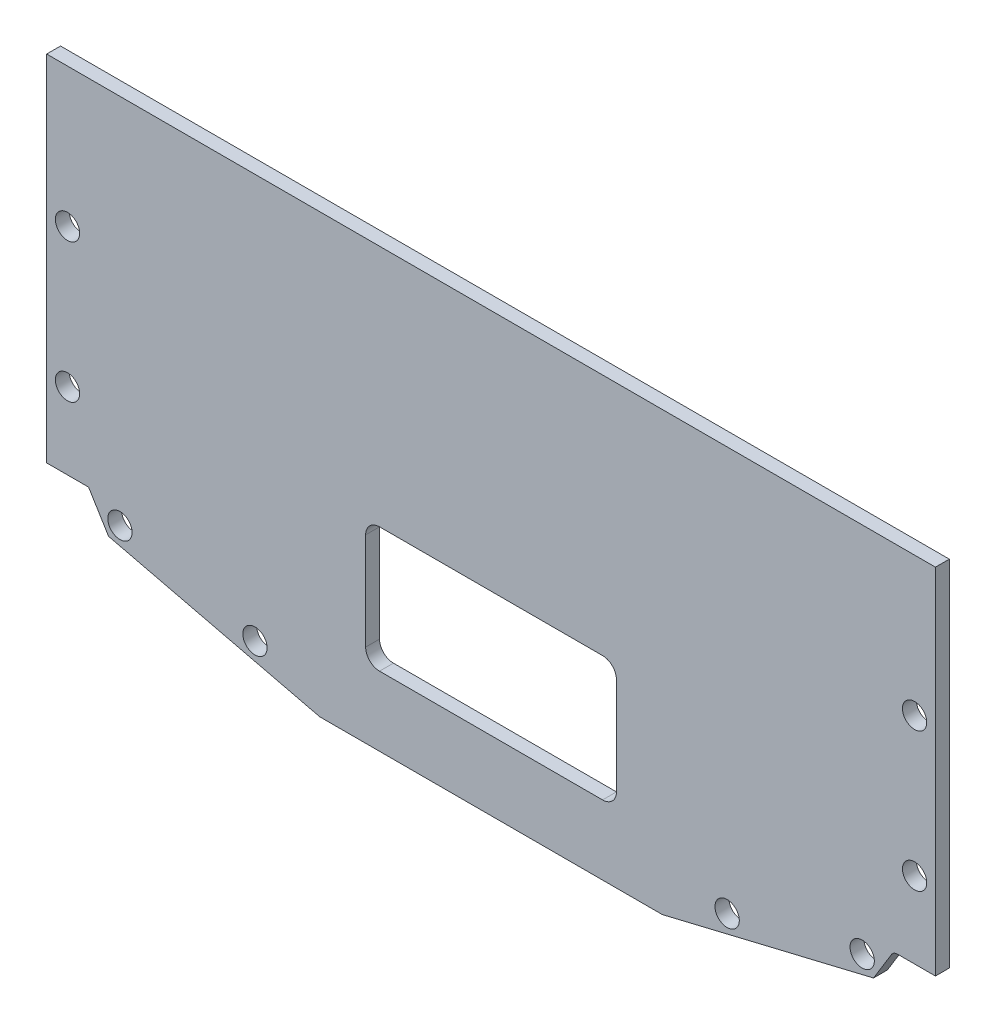
SolidWorks part; units mm, degrees
material "Thornel Mat VMA"
ref_plane "前视基准面" through (0, 0, 0) normal (0, 0, 1) x (1, 0, 0)
ref_plane "上视基准面" through (0, 0, 0) normal (0, 1, 0) x (1, 0, 0)
ref_plane "右视基准面" through (0, 0, 0) normal (1, 0, 0) x (0, 0, -1)
sketch "草图1" plane through (0, 0, 0) normal (0, 0, 1) x (1, 0, 0)
  line L0 (0, 63) -> (-21.7241, 8.6897) construction
  line L1 (0, 0) -> (128, 0)
  line L2 (0, 0) -> (0, 63)
  line L3 (0, 63) -> (128, 63)
  line L4 (128, 0) -> (128, 63)
  line L5 (-21.7241, 8.6897) -> (0, 0) construction
  line L6 (3, 63) -> (3, 43) construction
  line L7 (3, 43) -> (3, 23) construction
  line L8 (64, 63) -> (64, 191) construction
  circle A0 centre (3, 43) radius 1.75
  circle A1 centre (3, 23) radius 1.75
  circle A2 centre (125, 23) radius 1.75
  circle A3 centre (125, 43) radius 1.75
  dimension "D7" = 3.5
  dimension "D1" = 63
  dimension "D3" = 128
  dimension "D4" = 3
  dimension "D5" = 20
  dimension "D6" = 20
extrude "凸台-拉伸1" add sketch "草图1" along normal blind 2
sketch "草图2" plane through (0, 0, 2) normal (0, 0, 1) x (1, 0, 0)
  line L0 (50, 0) -> (30, 4.8) construction
  line L1 (0, 0) -> (128, 0) construction
  line L2 (30, 4.8) -> (10.5523, 9.4675) construction
  line L3 (10.5523, 9.4675) -> (0, 12) construction
  line L4 (0, 63) -> (0, 0) construction
  line L5 (64, 63) -> (64, 65.1855) construction
  line L6 (128, 63) -> (0, 63) construction
  circle A0 centre (10.5523, 9.4675) radius 1.75
  circle A1 centre (30, 4.8) radius 1.75
  circle A2 centre (98, 4.8) radius 1.75
  circle A3 centre (117.4477, 9.4675) radius 1.75
  dimension "D2" = 3.5
  dimension "D5" = 30
  dimension "D1" = 20
  dimension "D3" = 50
  dimension "D4" = 12
extrude "切除-拉伸1" cut sketch "草图2" against normal blind 10
sketch "草图3" plane through (0, 0, 2) normal (0, 0, 1) x (1, 0, 0)
  line L0 (12, 55) -> (12, 12.2052) construction
  line L1 (17, 55) -> (17, 11.0052)
  line L2 (7, 55) -> (7, 13.4052)
  line L3 (0, 63) -> (0, 0) construction
  line L4 (25.0604, 55) -> (24.2958, 9.2542) construction
  line L5 (30.0604, 55) -> (30.0604, 7.8707)
  line L6 (20.0604, 55) -> (20.0604, 10.2707)
  line L7 (37.8792, 52.5) -> (37.8792, 10.5) construction
  line L8 (42.8792, 52.5) -> (42.8792, 10.5)
  line L9 (32.8792, 52.5) -> (32.8792, 10.5)
  line L10 (50.9396, 52.5) -> (50.9396, 10.5) construction
  line L11 (55.9396, 52.5) -> (55.9396, 10.5)
  line L12 (45.9396, 52.5) -> (45.9396, 10.5)
  line L13 (64, 52.5) -> (64, 10.5) construction
  line L14 (69, 52.5) -> (69, 10.5)
  line L15 (59, 52.5) -> (59, 10.5)
  line L16 (77.0604, 52.5) -> (77.0604, 10.5) construction
  line L17 (82.0604, 52.5) -> (82.0604, 10.5)
  line L18 (72.0604, 52.5) -> (72.0604, 10.5)
  line L19 (90.1208, 52.5) -> (90.1208, 10.5) construction
  line L20 (95.1208, 52.5) -> (95.1208, 10.5)
  line L21 (85.1208, 52.5) -> (85.1208, 10.5)
  line L28 (128, 63) -> (0, 63) construction
  line L30 (7, 13.4052) -> (17, 11.0052)
  line L35 (20.0604, 10.2707) -> (30.0604, 7.8707)
  line L40 (64, 63) -> (64, 31.5) construction
  line L41 (64, 31.5) -> (128, 31.5) construction
  line L42 (128, 0) -> (128, 63) construction
  line L43 (37.8792, 52.5) -> (50.9396, 52.5) construction
  line L44 (50.9396, 52.5) -> (64, 52.5) construction
  line L45 (64, 52.5) -> (77.0604, 52.5) construction
  line L46 (77.0604, 52.5) -> (90.1208, 52.5) construction
  line L48 (102.9396, 55) -> (116, 55) construction
  line L49 (12, 55) -> (25.0604, 55) construction
  line L50 (25.0604, 55) -> (37.8792, 52.5) construction
  line L52 (102.9396, 55) -> (103.7042, 9.2542) construction
  line L53 (116, 55) -> (116, 12.2052) construction
  line L57 (107.9396, 10.2707) -> (97.9396, 7.8707)
  line L59 (121, 13.4052) -> (111, 11.0052)
  line L60 (107.9396, 55) -> (107.9396, 10.2707)
  line L61 (97.9396, 55) -> (97.9396, 7.8707)
  line L62 (121, 55) -> (121, 13.4052)
  line L63 (111, 55) -> (111, 11.0052)
  arc A0 (17, 55) -> (7, 55) centre (12, 55) ccw
  arc A2 (30.0604, 55) -> (20.0604, 55) centre (25.0604, 55) ccw
  arc A4 (42.8792, 52.5) -> (32.8792, 52.5) centre (37.8792, 52.5) ccw
  arc A5 (32.8792, 10.5) -> (42.8792, 10.5) centre (37.8792, 10.5) ccw
  arc A6 (55.9396, 52.5) -> (45.9396, 52.5) centre (50.9396, 52.5) ccw
  arc A7 (45.9396, 10.5) -> (55.9396, 10.5) centre (50.9396, 10.5) ccw
  arc A8 (69, 52.5) -> (59, 52.5) centre (64, 52.5) ccw
  arc A9 (59, 10.5) -> (69, 10.5) centre (64, 10.5) ccw
  arc A10 (82.0604, 52.5) -> (72.0604, 52.5) centre (77.0604, 52.5) ccw
  arc A11 (72.0604, 10.5) -> (82.0604, 10.5) centre (77.0604, 10.5) ccw
  arc A12 (95.1208, 52.5) -> (85.1208, 52.5) centre (90.1208, 52.5) ccw
  arc A13 (85.1208, 10.5) -> (95.1208, 10.5) centre (90.1208, 10.5) ccw
  circle A18 centre (30, 4.8) radius 1.75 construction
  circle A19 centre (10.5523, 9.4675) radius 1.75 construction
  arc A23 (97.9396, 55) -> (107.9396, 55) centre (102.9396, 55) cw
  arc A25 (111, 55) -> (121, 55) centre (116, 55) cw
  point P2 (12, 24)
  point P13 (25, 24)
  point P20 (37.8792, 31.5)
  point P27 (50.9396, 31.5)
  point P34 (64, 31.5)
  point P41 (77.0604, 31.5)
  point P48 (90.1208, 31.5)
  point P79 (25, 24)
  point P108 (103, 24)
  point P109 (116, 24)
  dimension "D2" = 5
  dimension "D5" = 8
  dimension "D8" = 3
  dimension "D11" = 5
  dimension "D1" = 12
  dimension "D7" = 3
  dimension "D12" = 42
extrude "切除-拉伸2" cut sketch "草图3" against normal blind 10
sketch "草图4" plane through (0, 0, 2) normal (0, 0, 1) x (1, 0, 0)
  line L0 (0, 0) -> (128, 0) construction
  line L1 (45.9396, 28) -> (82.0604, 28)
  line L2 (45.9396, 28) -> (45.9396, 0)
  line L3 (45.9396, 0) -> (82.0604, 0)
  line L4 (82.0604, 28) -> (82.0604, 0)
  line L5 (82.0604, 10.5) -> (82.0604, 52.5) construction
  line L6 (45.9396, 52.5) -> (45.9396, 10.5) construction
  dimension "D1" = 28
extrude "切除-拉伸3" cut sketch "草图4" against normal blind 10
sketch "草图5" plane through (0, 0, 2) normal (0, 0, 1) x (1, 0, 0)
  line L0 (45.9396, 52.5) -> (45.9396, 0) construction
  line L1 (45.9396, 28) -> (82.0604, 28)
  line L2 (45.9396, 28) -> (45.9396, 32)
  line L3 (45.9396, 32) -> (82.0604, 32)
  line L4 (82.0604, 28) -> (82.0604, 32)
  line L5 (82.0604, 0) -> (82.0604, 52.5) construction
  line L6 (72.0604, 28) -> (69, 28) construction
  dimension "D1" = 4
extrude "凸台-拉伸2" add sketch "草图5" against normal up to surface (2 mm away) up to face at (64, 35.5, 0)
sketch "草图6" plane through (0, 0, 2) normal (0, 0, 1) x (1, 0, 0)
  line L1 (0, 0) -> (6, 0)
  line L2 (0, 0) -> (0, 8)
  line L3 (0, 8) -> (6, 8)
  line L4 (6, 0) -> (6, 8)
  line L5 (128, 0) -> (122, 0)
  line L6 (128, 0) -> (128, 8)
  line L7 (128, 8) -> (122, 8)
  line L8 (122, 0) -> (122, 8)
  dimension "D1" = 6
  dimension "D2" = 8
extrude "切除-拉伸4" cut sketch "草图6" against normal blind 10
sketch "草图7" plane through (0, 0, 2) normal (0, 0, 1) x (1, 0, 0)
  line L0 (6, 8) -> (39.3333, 0)
  line L1 (6, 0) -> (45.9396, 0) construction
  line L2 (39.3333, 0) -> (6, 0)
  line L3 (6, 0) -> (6, 8)
  line L4 (30.0604, 7.8707) -> (20.0604, 10.2707) construction
  line L5 (122, 8) -> (88.6667, 0)
  line L6 (82.0604, 0) -> (122, 0) construction
  line L7 (88.6667, 0) -> (122, 0)
  line L8 (122, 0) -> (122, 8) construction
  line L9 (122, 0) -> (122, 8)
extrude "切除-拉伸5" cut sketch "草图7" against normal blind 10
sketch "草图8" plane through (0, 0, 0) normal (0, 0, -1) x (-1, 0, 0)
  line L0 (-45.9396, 0) -> (-45.9396, 28) construction
  line L1 (-82.0604, 0) -> (-45.9396, 0)
  line L2 (-82.0604, 0) -> (-82.0604, 10)
  line L3 (-82.0604, 10) -> (-45.9396, 10)
  line L4 (-45.9396, 0) -> (-45.9396, 10)
  line L5 (-45.9396, 28) -> (-82.0604, 28) construction
  dimension "D1" = 18
extrude "凸台-拉伸3" add sketch "草图8" against normal up to surface (2 mm away) up to face at (64, 43.5, 2)
sketch "草图10" plane through (0, 0, 2) normal (0, 0, 1) x (1, 0, 0)
  line L0 (0, 63) -> (0, 8) construction
  line L1 (0, 12) -> (6, 12)
  line L2 (0, 12) -> (0, 8)
  line L3 (0, 8) -> (6, 8)
  line L4 (6, 12) -> (6, 8)
  line L5 (0, 12) -> (6, 8) construction
  line L6 (0, 8) -> (6, 12) construction
  point P4 (3, 10)
  dimension "D1" = 4
extrude "切除-拉伸6" cut sketch "草图10" against normal through all
ref_plane "基准面1" through (64, 0, 0) normal (1, 0, 0) x (0, 0, -1)
mirror "镜向4" about plane through (64, 0, 0) normal (1, 0, 0) of "切除-拉伸6"
chamfer "倒角1" distance 3 angle 45 2 edges at (6, 8, 1) (122, 8, 1) first distance on face at (22.6667, 4, 1) first distance on face at (105.3333, 4, 1)
fillet "圆角1" radius 1 1 edges at (121.9636, 12, 1)
sketch "草图11" plane through (0, 0, 2) normal (0, 0, 1) x (1, 0, 0)
  line L0 (30.0604, 7.8707) -> (30.0604, 55) construction
  line L1 (20.0604, 55) -> (20.0604, 10.2707) construction
  line L2 (20.0604, 10.2707) -> (30.0604, 7.8707) construction
  line L3 (7, 13.4052) -> (17, 11.0052) construction
  line L4 (17, 11.0052) -> (17, 55) construction
  line L5 (7, 55) -> (7, 13.4052) construction
  line L6 (30.0604, 7.8707) -> (30.0604, 55)
  line L7 (20.0604, 55) -> (20.0604, 10.2707)
  line L8 (20.0604, 10.2707) -> (30.0604, 7.8707)
  line L9 (7, 13.4052) -> (17, 11.0052)
  line L10 (17, 11.0052) -> (17, 55)
  line L11 (7, 55) -> (7, 13.4052)
  line L12 (82.0604, 32) -> (82.0604, 52.5) construction
  line L13 (82.0604, 32) -> (72.0604, 32) construction
  line L14 (72.0604, 52.5) -> (72.0604, 32) construction
  line L15 (69, 32) -> (69, 52.5) construction
  line L16 (69, 32) -> (59, 32) construction
  line L17 (59, 52.5) -> (59, 32) construction
  line L18 (45.9396, 52.5) -> (45.9396, 32) construction
  line L19 (55.9396, 32) -> (55.9396, 52.5) construction
  line L20 (55.9396, 32) -> (45.9396, 32) construction
  line L21 (42.8792, 10.5) -> (42.8792, 52.5) construction
  line L22 (32.8792, 52.5) -> (32.8792, 10.5) construction
  line L23 (82.0604, 32) -> (82.0604, 52.5)
  line L24 (82.0604, 32) -> (72.0604, 32)
  line L25 (72.0604, 52.5) -> (72.0604, 32)
  line L26 (69, 32) -> (69, 52.5)
  line L27 (69, 32) -> (59, 32)
  line L28 (59, 52.5) -> (59, 32)
  line L29 (45.9396, 52.5) -> (45.9396, 32)
  line L30 (55.9396, 32) -> (55.9396, 52.5)
  line L31 (55.9396, 32) -> (45.9396, 32)
  line L32 (42.8792, 10.5) -> (42.8792, 52.5)
  line L33 (32.8792, 52.5) -> (32.8792, 10.5)
  line L34 (85.1208, 52.5) -> (85.1208, 10.5) construction
  line L35 (95.1208, 10.5) -> (95.1208, 52.5) construction
  line L36 (111, 11.0052) -> (121, 13.4052) construction
  line L37 (121, 13.4052) -> (121, 55) construction
  line L38 (111, 55) -> (111, 11.0052) construction
  line L39 (107.9396, 10.2707) -> (107.9396, 55) construction
  line L40 (97.9396, 55) -> (97.9396, 7.8707) construction
  line L41 (97.9396, 7.8707) -> (107.9396, 10.2707) construction
  line L42 (85.1208, 52.5) -> (85.1208, 10.5)
  line L43 (95.1208, 10.5) -> (95.1208, 52.5)
  line L44 (111, 11.0052) -> (121, 13.4052)
  line L45 (121, 13.4052) -> (121, 55)
  line L46 (111, 55) -> (111, 11.0052)
  line L47 (107.9396, 10.2707) -> (107.9396, 55)
  line L48 (97.9396, 55) -> (97.9396, 7.8707)
  line L49 (97.9396, 7.8707) -> (107.9396, 10.2707)
  arc A0 (30.0604, 55) -> (20.0604, 55) centre (25.0604, 55) ccw construction
  arc A1 (17, 55) -> (7, 55) centre (12, 55) ccw construction
  arc A2 (30.0604, 55) -> (20.0604, 55) centre (25.0604, 55) ccw
  arc A3 (17, 55) -> (7, 55) centre (12, 55) ccw
  arc A4 (82.0604, 52.5) -> (72.0604, 52.5) centre (77.0604, 52.5) ccw construction
  arc A5 (69, 52.5) -> (59, 52.5) centre (64, 52.5) ccw construction
  arc A6 (55.9396, 52.5) -> (45.9396, 52.5) centre (50.9396, 52.5) ccw construction
  arc A7 (32.8792, 10.5) -> (42.8792, 10.5) centre (37.8792, 10.5) ccw construction
  arc A8 (42.8792, 52.5) -> (32.8792, 52.5) centre (37.8792, 52.5) ccw construction
  arc A9 (82.0604, 52.5) -> (72.0604, 52.5) centre (77.0604, 52.5) ccw
  arc A10 (69, 52.5) -> (59, 52.5) centre (64, 52.5) ccw
  arc A11 (55.9396, 52.5) -> (45.9396, 52.5) centre (50.9396, 52.5) ccw
  arc A12 (32.8792, 10.5) -> (42.8792, 10.5) centre (37.8792, 10.5) ccw
  arc A13 (42.8792, 52.5) -> (32.8792, 52.5) centre (37.8792, 52.5) ccw
  arc A14 (95.1208, 52.5) -> (85.1208, 52.5) centre (90.1208, 52.5) ccw construction
  arc A15 (85.1208, 10.5) -> (95.1208, 10.5) centre (90.1208, 10.5) ccw construction
  arc A16 (121, 55) -> (111, 55) centre (116, 55) ccw construction
  arc A17 (107.9396, 55) -> (97.9396, 55) centre (102.9396, 55) ccw construction
  arc A18 (95.1208, 52.5) -> (85.1208, 52.5) centre (90.1208, 52.5) ccw
  arc A19 (85.1208, 10.5) -> (95.1208, 10.5) centre (90.1208, 10.5) ccw
  arc A20 (121, 55) -> (111, 55) centre (116, 55) ccw
  arc A21 (107.9396, 55) -> (97.9396, 55) centre (102.9396, 55) ccw
extrude "凸台-拉伸4" add sketch "草图11" against normal up to surface (2 mm away) up to face at (64, 19, 0)
fillet "圆角2" radius 2 4 edges at (82.0604, 10, 1) (45.9396, 10, 1) (45.9396, 28, 1) (82.0604, 28, 1)
